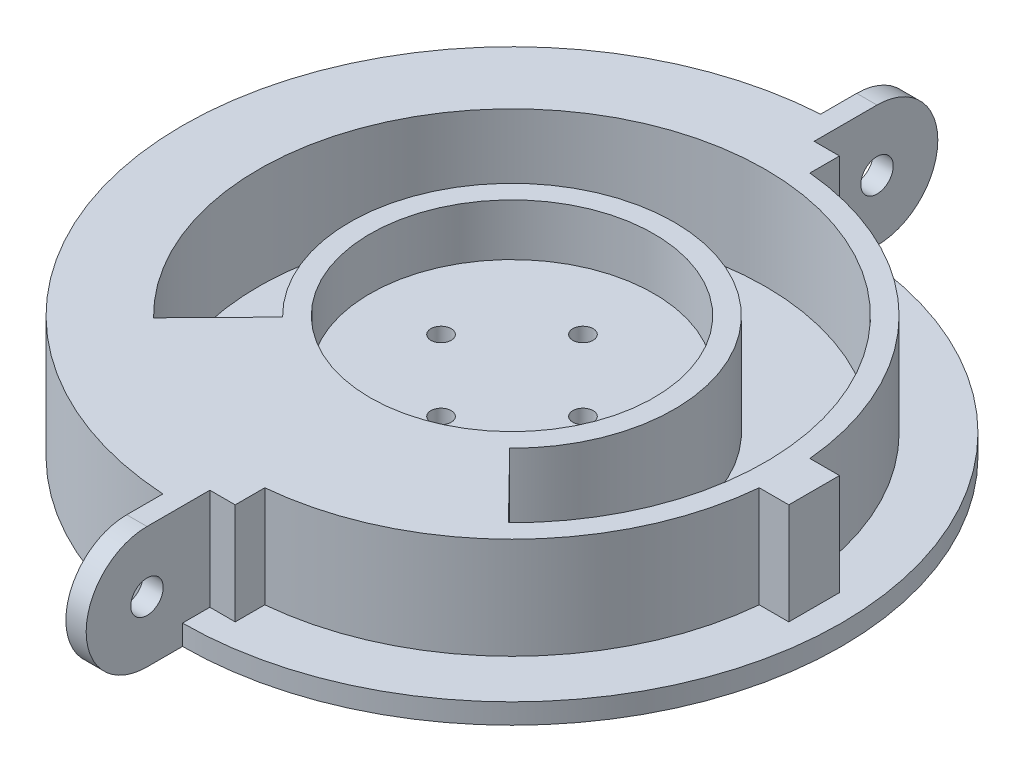
SolidWorks part; units mm, degrees
ref_plane "Front Plane" through (0, 0, 0) normal (0, 0, 1) x (1, 0, 0)
ref_plane "Top Plane" through (0, 0, 0) normal (0, 1, 0) x (1, 0, 0)
ref_plane "Right Plane" through (0, 0, 0) normal (1, 0, 0) x (0, 0, -1)
sketch "Sketch1" plane through (0, 0, 0) normal (0, 1, 0) x (1, 0, 0)
  line L0 (-17.5, -17.8536) -> (-11.2, -11.4263)
  line L1 (0, -55) -> (0, 55) construction
  line L2 (17.5, -17.8536) -> (11.2, -11.4263)
  line L4 (-17.5, -17.8536) -> (3.8221, -38.7535) construction
  circle A0 centre (0, 0) radius 27
  arc A1 (11.2, -11.4263) -> (-11.2, -11.4263) centre (0, 0) ccw
  arc A2 (17.5, -17.8536) -> (-17.5, -17.8536) centre (0, 0) ccw
  circle A3 centre (0, 0) radius 14
  arc A4 (16.5039, 11.7639) -> (14.35, -14.6399) centre (0.1913, -0.1952) cw construction
  circle A5 centre (0, 0) radius 19.9533 construction
  dimension "D1" = 54
  dimension "D2" = 2
  dimension "D3" = 9
  dimension "D4" = 2
  dimension "D5" = 35
extrude "Boss-Extrude1" add sketch "Sketch1" along normal blind 10
sketch "Sketch2" plane through (0, 0, 0) normal (0, -1, 0) x (1, 0, 0)
  circle A0 centre (0, 0) radius 32.5
  circle A1 centre (0, 0) radius 14 construction
  circle A2 centre (0, 0) radius 14 construction
  dimension "D1" = 65
extrude "Boss-Extrude2" add sketch "Sketch2" along normal blind 2
sketch "Sketch3" plane through (0, 0, 0) normal (0, 1, 0) x (1, 0, 0)
  line L0 (0, -5.5) -> (0, 5.5) construction
  line L1 (-2.5, 29.8) -> (2.5, 29.8)
  line L2 (-2.5, 29.8) -> (-2.5, 25.4032)
  line L3 (-2.5, 25.4032) -> (2.5, 25.4032)
  line L4 (2.5, 29.8) -> (2.5, 25.4032)
  line L5 (-2.5, 29.8) -> (2.5, 25.4032) construction
  line L6 (-2.5, 25.4032) -> (2.5, 29.8) construction
  line L7 (29.8, 2.5) -> (25.4032, 2.5)
  line L8 (29.8, 2.5) -> (29.8, -2.5)
  line L9 (29.8, -2.5) -> (25.4032, -2.5)
  line L10 (25.4032, 2.5) -> (25.4032, -2.5)
  line L11 (2.5, -29.8) -> (2.5, -25.4032)
  line L12 (2.5, -29.8) -> (-2.5, -29.8)
  line L13 (-2.5, -29.8) -> (-2.5, -25.4032)
  line L14 (2.5, -25.4032) -> (-2.5, -25.4032)
  line L15 (-29.8, -2.5) -> (-25.4032, -2.5)
  line L16 (-29.8, -2.5) -> (-29.8, 2.5)
  line L17 (-29.8, 2.5) -> (-25.4032, 2.5)
  line L18 (-25.4032, -2.5) -> (-25.4032, 2.5)
  circle A1 centre (0, 0) radius 27 construction
  point P0 (0, 27.6016)
  dimension "D2" = 29.8
  dimension "D1" = 5
  dimension "D3" = 4
extrude "Boss-Extrude3" add sketch "Sketch3" along normal blind 10
sketch "Sketch5" plane through (0, 0, 0) normal (0, 1, 0) x (1, 0, 0)
  line L0 (0, 29.8) -> (0, 32.5)
  line L1 (2.5, 29.8) -> (-2.5, 29.8) construction
  line L2 (0, -6.6) -> (0, 6.6) construction
  line L3 (0, -29.8) -> (0, -32.5)
  line L4 (0, 29.8) -> (-2.5, 29.8)
  line L5 (-2.5, 29.8) -> (-2.5, 26.884)
  line L6 (-26.884, 2.5) -> (-29.8, 2.5)
  line L7 (-29.8, 2.5) -> (-29.8, -2.5)
  line L8 (-29.8, -2.5) -> (-26.884, -2.5)
  line L9 (-2.5, -26.884) -> (-2.5, -29.8)
  line L10 (-2.5, -29.8) -> (0, -29.8)
  line L11 (-2.5, -29.8) -> (2.5, -29.8) construction
  circle A0 centre (0, 0) radius 32.5 construction
  arc A1 (0, 32.5) -> (0, -32.5) centre (0, 0) ccw
  arc A2 (-26.884, 2.5) -> (-2.5, 26.884) centre (0, 0) cw
  arc A3 (-26.884, -2.5) -> (-2.5, -26.884) centre (0, 0) ccw
extrude "Boss-Extrude4" add sketch "Sketch5" along normal up to surface (10 mm away) up to face at (0, 10, 0)
ref_plane "Plane1" through (0, 4.9, 0) normal (0, 1, 0) x (1, 0, 0)
sketch "Sketch6" plane through (0, 4.9, 0) normal (0, 1, 0) x (1, 0, 0)
  circle A0 centre (0, 0) radius 14
extrude "Boss-Extrude5" add sketch "Sketch6" against normal up to surface (4.9 mm away) up to face at (0, 0, 14)
sketch "Sketch4" plane through (0, -2, 0) normal (0, -1, 0) x (1, 0, 0)
  circle A0 centre (0, 0) radius 7 construction
  circle A1 centre (0, -7) radius 1
  circle A2 centre (-7, 0) radius 1
  circle A3 centre (0, 7) radius 1
  circle A4 centre (7, 0) radius 1
  point P14 (0, 0)
  dimension "D1" = 14
  dimension "D2" = 2
  dimension "D3" = 4
extrude "Cut-Extrude1" cut sketch "Sketch4" against normal through all both and the other way through all
sketch "Sketch7" plane through (0, 10, 0) normal (0, 1, 0) x (1, 0, 0)
  line L0 (11.2, -11.4263) -> (17.5, -17.8536) construction
  circle A0 centre (0, 0) radius 20.5 construction
  circle A1 centre (0, -20.5) radius 1.6
  point P5 (14.35, -14.6399)
  dimension "D1" = 3.2
extrude "Cut-Extrude2" [suppressed] cut sketch "Sketch7" against normal through all both and the other way through all
sketch "Sketch8" [suppressed] plane through (0, -2, 0) normal (0, -1, 0) x (1, 0, 0)
  line L0 (6.6, 0) -> (-6.6, 0) construction
  line L1 (-3.1177, 20.5) -> (-1.5588, 17.8)
  line L2 (-1.5588, 17.8) -> (1.5588, 17.8)
  line L3 (1.5588, 17.8) -> (3.1177, 20.5)
  line L4 (3.1177, 20.5) -> (1.5588, 23.2)
  line L5 (1.5588, 23.2) -> (-1.5588, 23.2)
  line L6 (-1.5588, 23.2) -> (-3.1177, 20.5)
  circle A0 centre (0, 20.5) radius 2.7 construction
  dimension "D1" = 5.4
extrude "Cut-Extrude3" [suppressed] cut sketch "Sketch8" against normal blind 4
sketch "Sketch9" plane through (0, 0, 0) normal (1, 0, 0) x (0, 0, -1)
  line L0 (32.5, 10) -> (-32.5, 10) construction
  line L1 (36, -2) -> (30.5, -2)
  line L3 (36, 10) -> (30.5, 10)
  line L4 (30.5, -2) -> (30.5, 10)
  line L5 (32.5, 10) -> (32.5, 0) construction
  arc A0 (36, -2) -> (36, 10) centre (36, 4) ccw
  circle A1 centre (36, 4) radius 1.6
  circle A2 centre (36, 4) radius 3 construction
  dimension "D4" = 3.2
  dimension "D5" = 6
  dimension "D1" = 3.5
  dimension "D2" = 2
  dimension "D3" = 12
extrude "Boss-Extrude6" add sketch "Sketch9" against normal blind 2
mirror "Mirror1" about plane through (0, 0, 0) normal (0, 0, 1) of "Boss-Extrude6"
